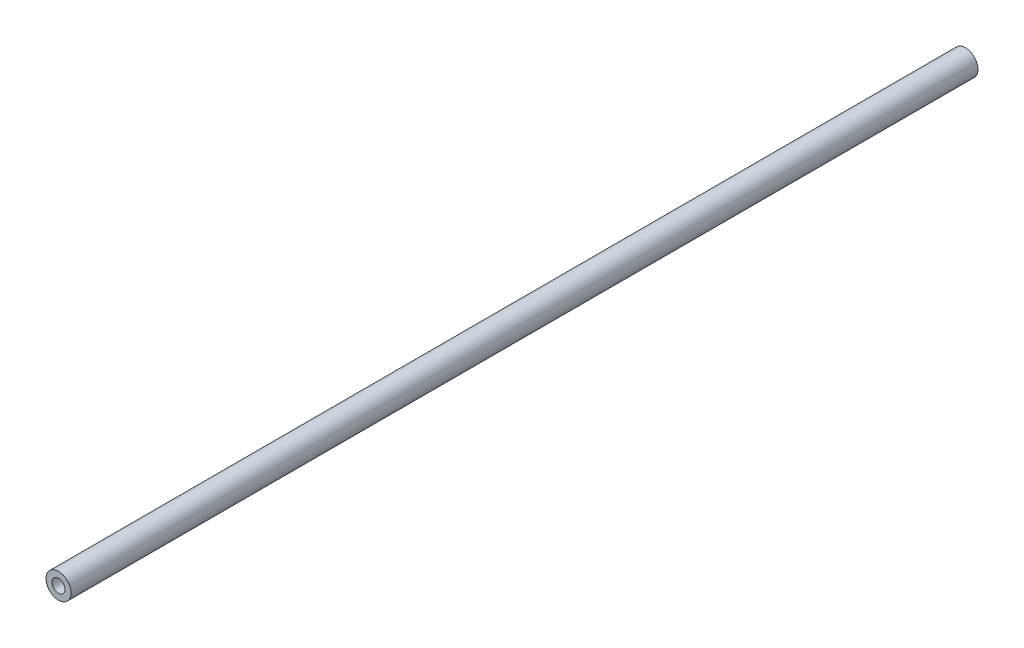
SolidWorks part; units mm, degrees
material "6061 Alloy"
ref_plane "Front Plane" through (0, 0, 0) normal (0, 0, 1) x (1, 0, 0)
ref_plane "Top Plane" through (0, 0, 0) normal (0, 1, 0) x (1, 0, 0)
ref_plane "Right Plane" through (0, 0, 0) normal (1, 0, 0) x (0, 0, -1)
sketch "Sketch1" plane through (0, 0, 0) normal (0, 0, 1) x (1, 0, 0)
  circle A0 centre (0, 0) radius 5
  dimension "D1" = 10
extrude "Boss-Extrude1" add sketch "Sketch1" along normal blind 362.5
hole_wizard "#6 (0.204) Diameter Hole1" positions "Sketch2" profile "Sketch3" hole size "#6" standard "ANSI Inch"
sketch "Sketch2" plane through (0, 0, 0) normal (0, 0, -1) x (-1, 0, 0)
  point P0 (0, 0)
sketch "Sketch3" plane through (0, 0, 0) normal (1, 0, 0) x (0, 1, 0)
  line L0 (0, 0) -> (0, 31.5567)
  line L1 (0, 31.5567) -> (2.5908, 30)
  line L2 (2.5908, 30) -> (2.5908, 0)
  line L5 (2.5908, 0) -> (0, 0)
  line L10 (0, 31.5567) -> (-2.5908, 30) construction
  line L11 (0, -6.35) -> (0, 107.95) construction
  dimension "Hole Dia." = 5.1816
  dimension "Hole Depth" = 30
  dimension "Drill Angle" = 118
hole_wizard "#6 (0.204) Diameter Hole2" positions "Sketch4" profile "Sketch5" hole size "#6" standard "ANSI Inch"
sketch "Sketch4" plane through (0, 0, 362.5) normal (0, 0, 1) x (1, 0, 0)
  point P0 (0, 0)
sketch "Sketch5" plane through (0, 0, 362.5) normal (1, 0, 0) x (0, -1, 0)
  line L0 (0, 0) -> (0, 31.5567)
  line L1 (0, 31.5567) -> (2.5908, 30)
  line L2 (2.5908, 30) -> (2.5908, 0)
  line L5 (2.5908, 0) -> (0, 0)
  line L10 (0, 31.5567) -> (-2.5908, 30) construction
  line L11 (0, -6.35) -> (0, 107.95) construction
  dimension "Hole Dia." = 5.1816
  dimension "Hole Depth" = 30
  dimension "Drill Angle" = 118
